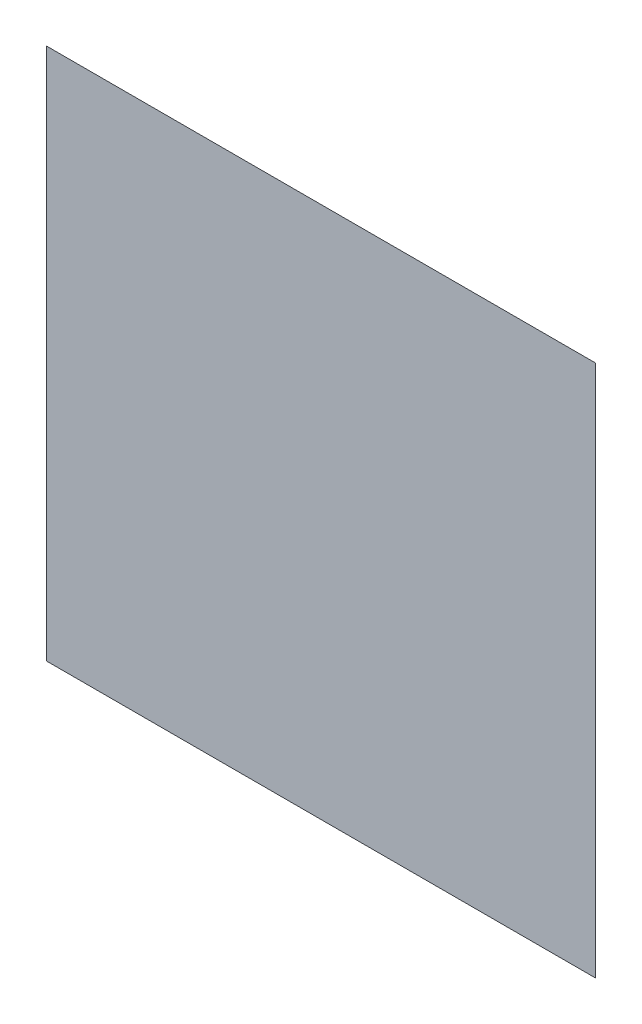
SolidWorks part; units mm, degrees
ref_plane "前视基准面" through (0, 0, 0) normal (0, 0, 1) x (1, 0, 0)
ref_plane "上视基准面" through (0, 0, 0) normal (0, 1, 0) x (1, 0, 0)
ref_plane "右视基准面" through (0, 0, 0) normal (1, 0, 0) x (0, 0, -1)
sketch "草图1" plane through (0, 0, 0) normal (0, 0, 1) x (1, 0, 0)
  line L0 (107.0902, 126.3962) -> (-17.0814, 126.3962) construction
  line L1 (-22.4956, 126.3962) -> (112.5044, 126.3962)
  line L2 (-22.4956, 126.3962) -> (-22.4956, 1.3962)
  line L3 (-22.4956, 1.3962) -> (112.5044, 1.3962)
  line L4 (112.5044, 126.3962) -> (112.5044, 1.3962)
  line L5 (-22.4956, 120.982) -> (-22.4956, 94.3104) construction
  line L6 (112.5044, 94.3104) -> (112.5044, 120.982) construction
  line L7 (-17.0814, 1.3962) -> (107.0902, 1.3962) construction
ref_plane "基准面1" through (0, 0, 100) normal (0, 0, 1) x (1, 0, 0)
sketch "草图2" plane through (0, 0, 100) normal (0, 0, 1) x (1, 0, 0)
  line L0 (-22.4956, 126.3962) -> (112.5044, 126.3962) construction
  line L1 (-122.4956, 226.3962) -> (212.5044, 226.3962)
  line L2 (-122.4956, 226.3962) -> (-122.4956, -98.6038)
  line L3 (-122.4956, -98.6038) -> (212.5044, -98.6038)
  line L4 (212.5044, 226.3962) -> (212.5044, -98.6038)
  line L5 (112.5044, 126.3962) -> (112.5044, 1.3962) construction
  line L6 (-22.4956, 126.3962) -> (-22.4956, 1.3962) construction
  line L7 (-22.4956, 1.3962) -> (112.5044, 1.3962) construction
  dimension "D1" = 100
  dimension "D2" = 100
  dimension "D3" = 100
  dimension "D4" = 100
loft "放样1" add profiles "草图2", "草图1" connector at (-122.4956, 226.3962, 100) connector at (-22.4956, 126.3962, 0)
